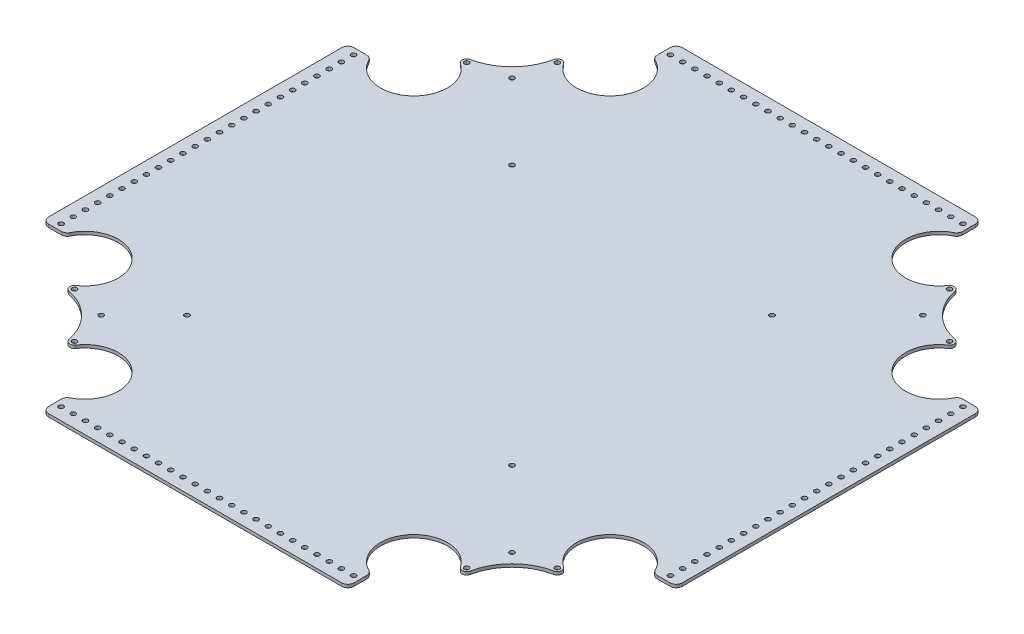
SolidWorks part; units mm, degrees
material "PC High Viscosity"
ref_plane "Front Plane" through (0, 0, 0) normal (0, 0, 1) x (1, 0, 0)
ref_plane "Top Plane" through (0, 0, 0) normal (0, 1, 0) x (1, 0, 0)
ref_plane "Right Plane" through (0, 0, 0) normal (1, 0, 0) x (0, 0, -1)
sketch "Sketch1" plane through (0, 0, 0) normal (0, 1, 0) x (1, 0, 0)
  line L1 (330.2, 330.2) -> (-330.2, 330.2)
  line L2 (330.2, 330.2) -> (330.2, -330.2)
  line L3 (330.2, -330.2) -> (-330.2, -330.2)
  line L4 (-330.2, 330.2) -> (-330.2, -330.2)
  line L5 (330.2, 330.2) -> (-330.2, -330.2) construction
  line L6 (330.2, -330.2) -> (-330.2, 330.2) construction
  point P0 (0, 0)
  dimension "D1" = 660.4
extrude "Boss-Extrude1" add sketch "Sketch1" along normal mid plane 3.175
sketch "Sketch2" plane through (0, 1.5875, 0) normal (0, 1, 0) x (1, 0, 0)
  line L0 (-330.2, -330.2) -> (330.2, -330.2) construction
  line L1 (-330.2, 330.2) -> (-330.2, -330.2) construction
  circle A0 centre (-317.5, -317.5) radius 2.4892
  dimension "D1" = 4.9784
  dimension "D2" = 12.7
  dimension "D3" = 12.7
extrude "Cut-Extrude1" cut sketch "Sketch2" against normal through all
pattern_linear "LPattern1" count 51 spacing 12.7 along (0, 0, -1) count 51 spacing 12.7 along (1, 0, 0) of "Cut-Extrude1" pattern seed only yes
pattern_linear "LPattern2" count 51 spacing 12.7 along (0, 0, -1) of face at (317.5, -1.5875, 319.9892)
pattern_linear "LPattern3" count 50 spacing 12.7 along (1, 0, 0) of face at (-317.5, -1.5875, -315.0108)
sketch "Sketch4" plane through (0, -1.5875, 0) normal (0, -1, 0) x (-1, 0, 0)
  line L0 (-330.2, 159.131) -> (-306.3652, 159.131)
  line L1 (-330.2, -330.2) -> (-330.2, 330.2) construction
  line L2 (-320.675, 160.7185) -> (-314.325, 160.7185) construction
  line L3 (-159.131, 330.2) -> (-159.131, 306.3652)
  line L4 (-330.2, 330.2) -> (330.2, 330.2) construction
  line L5 (-159.131, 330.2) -> (-330.2, 330.2)
  line L6 (-330.2, 330.2) -> (-330.2, 159.131)
  circle A0 centre (-263.525, 263.525) radius 55.5625
  arc A1 (-232.9401, 309.912) -> (-319.0875, 263.525) centre (-263.525, 263.525) ccw construction
  circle A2 centre (-171.45, 273.685) radius 34.925
  circle A3 centre (-273.685, 171.45) radius 34.925
  arc A4 (-140.716, 273.685) -> (-171.45, 304.419) centre (-171.45, 273.685) ccw construction
  arc A5 (-304.8, 171.45) -> (-251.6834, 149.4484) centre (-273.685, 171.45) ccw construction
  arc A6 (-254.2153, 200.4446) -> (-252.5049, 209.0663) centre (-251.5604, 204.3984) cw
  arc A7 (-209.0663, 252.5049) -> (-200.4446, 254.2153) centre (-204.3984, 251.5604) cw
  dimension "D1" = 69.85
  dimension "D2" = 1.5875
  dimension "D3" = 4.7625
extrude "Cut-Extrude2" cut sketch "Sketch4" against normal through all contours A0 A7 A2 L3 L5 L6 L0 A3 A6 | A0 | A3 | A2 region at (327.7807, -1.5875, -244.6655) region at (273.685, -1.5875, -171.45) region at (263.525, -1.5875, -263.525) region at (171.45, -1.5875, -273.685)
mirror "Mirror2" about plane through (0, 0, 0) normal (1, 0, 0) of "Cut-Extrude2"
mirror "Mirror3" about plane through (0, 0, 0) normal (0, 0, 1) of "Cut-Extrude2", "Mirror2"
fillet "Fillet1" radius 6.35 16 edges at (-330.2, 0, -159.131) (-306.3652, 0, -159.131) (-159.131, 0, -306.3652) (-159.131, 0, -330.2) (159.131, 0, -330.2) (159.131, 0, -306.3652) (306.3652, 0, -159.131) (330.2, 0, -159.131) (330.2, 0, 159.131) (306.3652, 0, 159.131) (159.131, 0, 306.3652) (159.131, 0, 330.2) (-159.131, 0, 330.2) (-159.131, 0, 306.3652) (-330.2, 0, 159.131) (-306.3652, 0, 159.131)
sketch "Sketch5" plane through (0, -1.5875, 0) normal (0, -1, 0) x (1, 0, 0)
  circle A0 centre (135.4667, 135.4667) radius 2.4892 construction
  circle A1 centre (135.4667, -135.4667) radius 2.4892 construction
  circle A2 centre (-135.4667, -135.4667) radius 2.4892 construction
  circle A3 centre (-169.3333, 169.3333) radius 2.4892 construction
  circle A4 centre (135.4667, 135.4667) radius 2.4892
  circle A5 centre (135.4667, -135.4667) radius 2.4892
  circle A6 centre (-135.4667, -135.4667) radius 2.4892
  circle A8 centre (-169.3333, 169.3333) radius 2.4892
extrude "Cut-Extrude3" cut sketch "Sketch5" against normal through all
sketch "Sketch6" plane through (0, 1.5875, 0) normal (0, 1, 0) x (1, 0, 0)
  line L0 (0, 0) -> (0, 23.3452) construction
  line L1 (0, 0) -> (30.1444, 0) construction
  circle A0 centre (-251.5604, -204.3984) radius 2.4892
  circle A1 centre (-204.3984, -251.5604) radius 2.4892
  circle A2 centre (-169.3333, -169.3333) radius 2.4892 construction
  circle A4 centre (-214.0672, -214.0672) radius 2.4892
  arc A5 (-251.5604, -204.3984) -> (-204.3984, -251.5604) centre (-241.0079, -241.0079) cw construction
  arc A6 (251.5604, -204.3984) -> (204.3984, -251.5604) centre (241.0079, -241.0079) ccw construction
  circle A7 centre (214.0672, -214.0672) radius 2.4892
  circle A8 centre (204.3984, -251.5604) radius 2.4892
  circle A9 centre (251.5604, -204.3984) radius 2.4892
  arc A10 (251.5604, 204.3984) -> (204.3984, 251.5604) centre (241.0079, 241.0079) cw construction
  arc A11 (-251.5604, 204.3984) -> (-204.3984, 251.5604) centre (-241.0079, 241.0079) ccw construction
  circle A12 centre (251.5604, 204.3984) radius 2.4892
  circle A13 centre (204.3984, 251.5604) radius 2.4892
  circle A14 centre (214.0672, 214.0672) radius 2.4892
  circle A15 centre (-214.0672, 214.0672) radius 2.4892
  circle A16 centre (-204.3984, 251.5604) radius 2.4892
  circle A17 centre (-251.5604, 204.3984) radius 2.4892
  dimension "D1" = 38.1
extrude "Cut-Extrude4" cut sketch "Sketch6" against normal through all both
